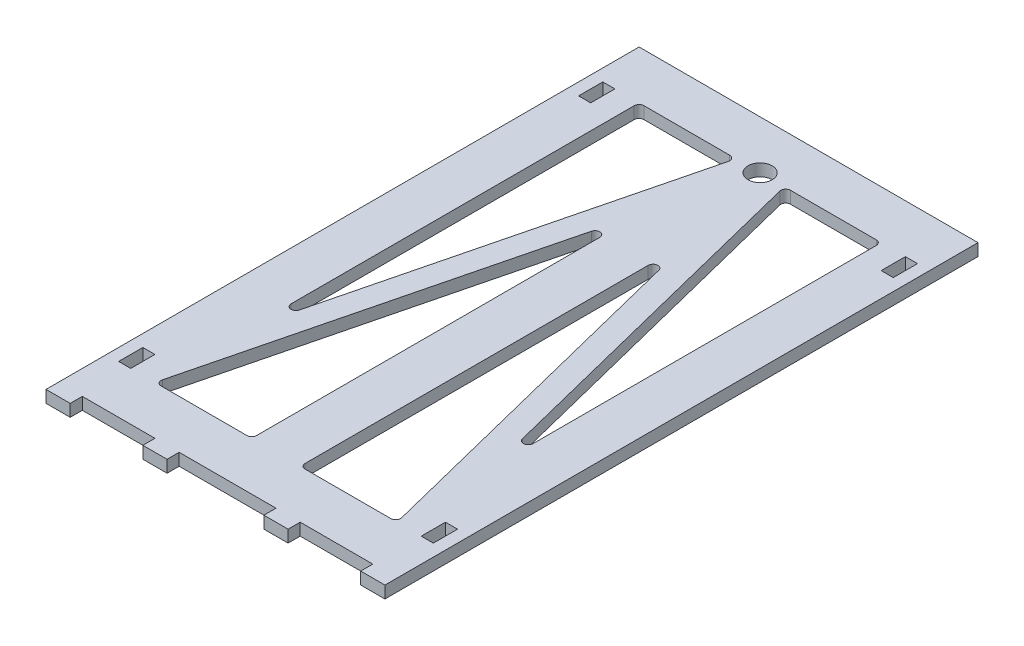
SolidWorks part; units mm, degrees
material "Beech"
ref_plane "Front Plane" through (0, 0, 0) normal (0, 0, 1) x (1, 0, 0)
ref_plane "Top Plane" through (0, 0, 0) normal (0, 1, 0) x (1, 0, 0)
ref_plane "Right Plane" through (0, 0, 0) normal (1, 0, 0) x (0, 0, -1)
sketch "Sketch1" plane through (0, 0, 0) normal (0, 1, 0) x (1, 0, 0)
  line L0 (0, 0) -> (177.8, 0)
  line L1 (0, 0) -> (0, 304.8)
  line L2 (177.8, 0) -> (177.8, 304.8)
  line L3 (0, 304.8) -> (177.8, 304.8)
  line L4 (0, 0) -> (12.7, 0)
  line L5 (0, 0) -> (0, -6.35)
  line L6 (12.7, 0) -> (12.7, -6.35)
  line L7 (0, -6.35) -> (12.7, -6.35)
  line L8 (177.8, 0) -> (165.1, 0)
  line L9 (177.8, 0) -> (177.8, -6.35)
  line L10 (165.1, 0) -> (165.1, -6.35)
  line L11 (177.8, -6.35) -> (165.1, -6.35)
  line L12 (127, 0) -> (114.3, 0)
  line L13 (127, 0) -> (127, -6.35)
  line L14 (114.3, 0) -> (114.3, -6.35)
  line L15 (127, -6.35) -> (114.3, -6.35)
  line L16 (50.8, 0) -> (63.5, 0)
  line L17 (50.8, 0) -> (50.8, -6.35)
  line L18 (63.5, 0) -> (63.5, -6.35)
  line L19 (50.8, -6.35) -> (63.5, -6.35)
  line L20 (165.1, 279.4) -> (171.45, 279.4)
  line L21 (165.1, 279.4) -> (165.1, 266.7)
  line L22 (171.45, 279.4) -> (171.45, 266.7)
  line L23 (165.1, 266.7) -> (171.45, 266.7)
  line L24 (6.35, 279.4) -> (12.7, 279.4)
  line L25 (6.35, 279.4) -> (6.35, 266.7)
  line L26 (12.7, 279.4) -> (12.7, 266.7)
  line L27 (6.35, 266.7) -> (12.7, 266.7)
  line L28 (6.35, 38.1) -> (12.7, 38.1)
  line L29 (6.35, 38.1) -> (6.35, 25.4)
  line L30 (12.7, 38.1) -> (12.7, 25.4)
  line L31 (6.35, 25.4) -> (12.7, 25.4)
  line L32 (165.1, 38.1) -> (171.45, 38.1)
  line L33 (165.1, 38.1) -> (165.1, 25.4)
  line L34 (171.45, 38.1) -> (171.45, 25.4)
  line L35 (165.1, 25.4) -> (171.45, 25.4)
  line L36 (101.6, 279.4) -> (152.4, 279.4)
  line L37 (152.4, 279.4) -> (152.4, 76.2)
  line L38 (152.4, 76.2) -> (101.6, 279.4)
  line L39 (101.6, 228.6) -> (101.6, 25.4)
  line L40 (101.6, 25.4) -> (152.4, 25.4)
  line L41 (152.4, 25.4) -> (101.6, 228.6)
  line L42 (76.2, 279.4) -> (25.4, 279.4)
  line L43 (25.4, 279.4) -> (25.4, 76.2)
  line L44 (25.4, 76.2) -> (76.2, 279.4)
  line L45 (76.2, 228.6) -> (76.2, 25.4)
  line L46 (76.2, 25.4) -> (25.4, 25.4)
  line L47 (25.4, 25.4) -> (76.2, 228.6)
  circle A0 centre (88.9, 279.4) radius 6.35
  point P21 (88.9, 304.8)
  dimension "D8" = 12.7
  dimension "D1" = 177.8
  dimension "D2" = 6.35
  dimension "D3" = 12.7
  dimension "D4" = 50.8
  dimension "D5" = 50.8
  dimension "D6" = 304.8
  dimension "D7" = 25.4
  dimension "D9" = 25.4
  dimension "D10" = 25.4
  dimension "D11" = 12.7
  dimension "D12" = 12.7
  dimension "D13" = 203.2
  dimension "D14" = 50.8
  dimension "D15" = 50.8
extrude "Front Panel" add sketch "Sketch1" along normal blind 6.35 contours L3 L1 L0 L2 A0 L35 L33 L32 L34 L31 L29 L28 L30 L27 L25 L24 L26 L23 L21 L20 L22 | L5 L7 L6 L0 | L17 L19 L18 L0 | L15 L13 L0 L14 | L11 L9 L0 L10 region at (88.9, 0, -151.9139) region at (6.35, 0, 3.175) region at (57.15, 0, 3.175) region at (171.45, 0, 3.175) region at (120.65, 0, 3.175)
fillet "Fillet1" radius 2.54 12 edges at (25.4, 3.175, -76.2) (152.4, 3.175, -76.2) (25.4, 3.175, -25.4) (76.2, 3.175, -25.4) (101.6, 3.175, -25.4) (152.4, 3.175, -25.4) (76.2, 3.175, -228.6) (101.6, 3.175, -228.6) (25.4, 3.175, -279.4) (76.2, 3.175, -279.4) (101.6, 3.175, -279.4) (152.4, 3.175, -279.4)
equation "\"CageLeftBottomEdge\"=22.11mm"
equation "\"CageLeftTopEdge\"=22.11mm"
equation "\"CageRightBottomEdge\"=21.63mm"
equation "\"CageRightTopEdge\"=21.63mm"
equation "\"CageHeight\"=86.04mm"
equation "\"CageLength\"=73.76mm"
equation "\"CageTopScrewClearance\"=10mm"
equation "\"CageBottomScrewClearance\"=25mm"
equation "\"CageLeftTopDepth\"= 11.65mm"
equation "\"CageLeftBottomDepth\"=11.11mm"
equation "\"CageLeftTopHeight\"=8.56175mm"
equation "\"CageLeftBottomHeight\"=16mm"
equation "\"CageRightTopDepth\"= 11.05mm"
equation "\"CageRightBottomDepth\"=10.58mm"
equation "\"CageRightTopHeight\"=9.6mm"
equation "\"CageRightBottomHeight\"=15.49mm"
equation "\"CageLeftTopChannelDepth\"=2.41908mm"
equation "\"CageLeftBottomChannelDepth\"=2.588mm"
equation "\"CageLeftChannelHeight\"=11.7mm"
equation "\"CageRightTopChannelDepth\"=2.32mm"
equation "\"CageRightBottomChannelDepth\"=2.318mm"
equation "\"CageRightChannelHeight\"=10mm"
equation "\"CageChanRelHeight\"=23.99mm"
equation "\"CageChanRelDepth\"=5.492mm"
equation "\"CageChamberRadius\"=16.261mm"
equation "\"CageScrewDiameter\"=4.8mm"
equation "\"CageSetScrewDiameter\"=3.5mm"
equation "\"CageAxleRadius\"=6.639mm"
equation "\"CageAxleKeyHeight\"=1.619mm"
equation "\"CageAxleKeyWidth\"=2.662mm"
equation "\"CageHoseWindowWidth\"=16.29mm"
equation "\"CageHoseWindowHeight\"=26.5mm"
equation "\"CageHoseWindow-Edge\"=8.89mm"
equation "\"CageScrew-VerticalEdge\"=5.0mm"
equation "\"CageScrew-HorizontalEdge\"=7.5mm"
equation "\"CageScrew-HoseCornerScrewEdge\"=4.45mm"
equation "\"CageAxle-BottomEdge\"=56.05mm"
equation "\"CageAxle-FrontEdge\"=46.03mm"
equation "\"CageBackSetScrew-Axle\"=40mm"
equation "\"CageFrontSetScrew-Axle\"=22mm"
equation "\"CageVelocityWindow-BackEdge\"=34.8mm"
equation "\"CageVelocityWindow-BottomEdge\"=27.55mm"
equation "\"CageVelocityWindowHeight\"=22.29mm"
equation "\"CageVelocityWindowWidth\"=12.61mm"
equation "\"TriggerSlot-BottomEdge\"=6.35mm"
equation "\"TriggerSlot-FrontEdge\"=15mm"
equation "\"TriggerSlotSize\"=6.7mm"
equation "\"TriggerRackOffset\"=.236224in"
equation "\"TriggerSlotSizeInt\"=.25in"
equation "\"MotorMountLegLength\"=.25in"
equation "\"GearOffset\"=.264907in"
equation "\"TriggerSlotSpacing\"=.25in"
equation "\"TriggerMiniSlotWidth\"=3.5mm"
equation "\"TriggerRackWidth\"=6.5mm"
equation "\"whitemotordepth\"=11.27mm"
equation "\"whitemotorbackdepth\"=3.845mm"
equation "\"whitemotoraxledepth\" = 3.5mm"
equation "\"whitemotoraxleoffset\"=11.4mm"
equation "\"whitemotorwidth\"=12.07mm"
equation "\"whitemotorheight\"=16.68mm"
equation "\"whitemotorcylinderlength\" =13.04mm"
equation "\"whitemotorcylinderradius\"=3.845mm"
equation "\"whitemotorcylinderoffset\"=2.35mm"
equation "\"whitemotorcutoutlength\"=1.88mm"
equation "\"whitemotorouterrad\"=5mm"
equation "\"whitemotorinnerrad\"=2.95mm"
equation "\"elasticracklength\"=2in"
equation "\"elasticrackpegsize\"=.25in"
equation "\"elasticrackpegbuffer\"=.125in"
equation "\"elasticrackpegspacing\"=1.76476378in"
equation "\"elasticbaybuffer\"=.25in"
equation "\"elasticdepth\"=.125in"
equation "\"elasticbaydepth\"=.75in"
equation "\"motormountwidth\"=12mm"
equation "\"motormountcornerfillet\"=3mm"
equation "\"pandiscradius\"=14in"
equation "\"towermaterialwidth\"=.25in"
equation "\"towerslotlength\"=.5in"
equation "\"towermarkerspace\"=5in"
equation "\"towerslothorizoffset\"=1in"
equation "\"towerslothorizspacing\"=2in"
equation "\"towerslotvertoffset\"=3in"
equation "\"towerslotvertspacing\"=1in"
equation "\"towerheight\"=12in"
equation "\"towerupslot\"=1in"
equation "\"D1@Sketch1\"=(\"towerslothorizoffset\"+\"towerslothorizspacing\"+\"towerslotlength\")*2"
equation "\"D2@Sketch1\"=\"towermaterialwidth\""
equation "\"D3@Sketch1\"=\"towerslotlength\""
equation "\"D4@Sketch1\"=\"towerslothorizspacing\""
equation "\"D5@Sketch1\"=\"towerslothorizspacing\""
equation "\"D6@Sketch1\"=\"towerheight\""
equation "\"D7@Sketch1\"=\"towerupslot\""
equation "\"toweraxle\"=.5in"
equation "\"D8@Sketch1\"=\"toweraxle\""
equation "\"D9@Sketch1\"=\"towerupslot\""
equation "\"D10@Sketch1\"= \"towerupslot\""
equation "\"D1@Front Panel\"=\"towermaterialwidth\""
equation "\"stepperouterrad\"=10mm"
equation "\"stepperscrewsize\"=3.45mm"
equation "\"stepperscrewc2c\"=49.5mm"
equation "\"stepperdepthoffset\"=24mm"
equation "\"stepperhorizoffset\"=22.91mm"
equation "\"shaftslotOD\"=18.8mm"
equation "\"shaftslotID\"=13.28mm"
equation "\"shaftkeywidth\"=2.67mm"
equation "\"shaftkeydepth\"=1.8mm"
equation "\"shaftcollartotaldepth\"=12.5mm"
equation "\"shaftsquaredepth\"=6mm"
equation "\"shaftsetscrewsize\"=3.5mm"
equation "\"shaftkeytightdepth\"=1.85mm"
equation "\"shaftslottightID\"=12.78mm"
equation "\"shaftsetscrewoffset\"=9mm"
equation "\"cagecollartotaldepth\"=10mm"
equation "\"cagecollartotalwidth\"=35mm"
equation "\"cagecollarbasedepth\"=4mm"
equation "\"D11@Sketch1\"=\"toweraxle\""
equation "\"D12@Sketch1\"=\"toweraxle\""
equation "\"towerspeedwidth\"=2in"
equation "\"D15@Sketch1\"=\"towerspeedwidth\""
equation "\"towerspeedheight\"=8in"
equation "\"D13@Sketch1\"=\"towerspeedheight\""
equation "\"towerspeedgap\"=2in"
equation "\"D14@Sketch1\"=\"towerspeedgap\""
equation "\"gearhubintdiam\"=30mm"
equation "\"gearhubintwid\"=15mm"
equation "\"stepperaxleflat\"=.037in"
equation "\"stepperaxlerad\"=0.11811024in"
equation "\"ajaxaxlesize\"=3.87mm"
equation "\"ajaxinnercut\"=2.3mm"
equation "\"ajaxwidth\"=6.1mm"
equation "\"ajaxdiametral\"=25.8854"
equation "\"ajaxcutoutdepth\"=2.3mm"
equation "\"ajax4020gap\"=29.5mm"
equation "\"ajax4010gap\"=24.5mm"
equation "\"ajax20hubbuffer\"=6.1mm"
equation "\"ajax20hubholeoffset\"=.19685in"
equation "\"ajax20hubholesize\"=.059055in"
equation "\"ajax20cutoutint\"=13.4mm"
equation "\"ajax40hubholesize\"=7.21mm"
equation "\"ajax40hubholeoffset\"=10mm"
equation "\"ajax40hubbuffer\"=8.9mm"
equation "\"ajax40cutoutint\"=32.6mm"
equation "\"bearingpandiscrad\"=6.8in"
equation "\"bearingpandiscang\"=48.75deg"
equation "\"bearingclearholedist\"=4.7345in"
equation "\"bearingclearholesize\"=.5in"
equation "\"bearingclearholeang\"=22.5deg"
equation "\"bearingmountholedist\"=4.25in"
equation "\"bearingwirehole\"=1.5in"
equation "\"no6diam\"=.146in"
equation "\"shortconangle\"=20deg"
equation "\"shortconlen\"=.875in"
equation "\"longconlen\"=1.25in"
equation "\"longconangle\"=15deg"
